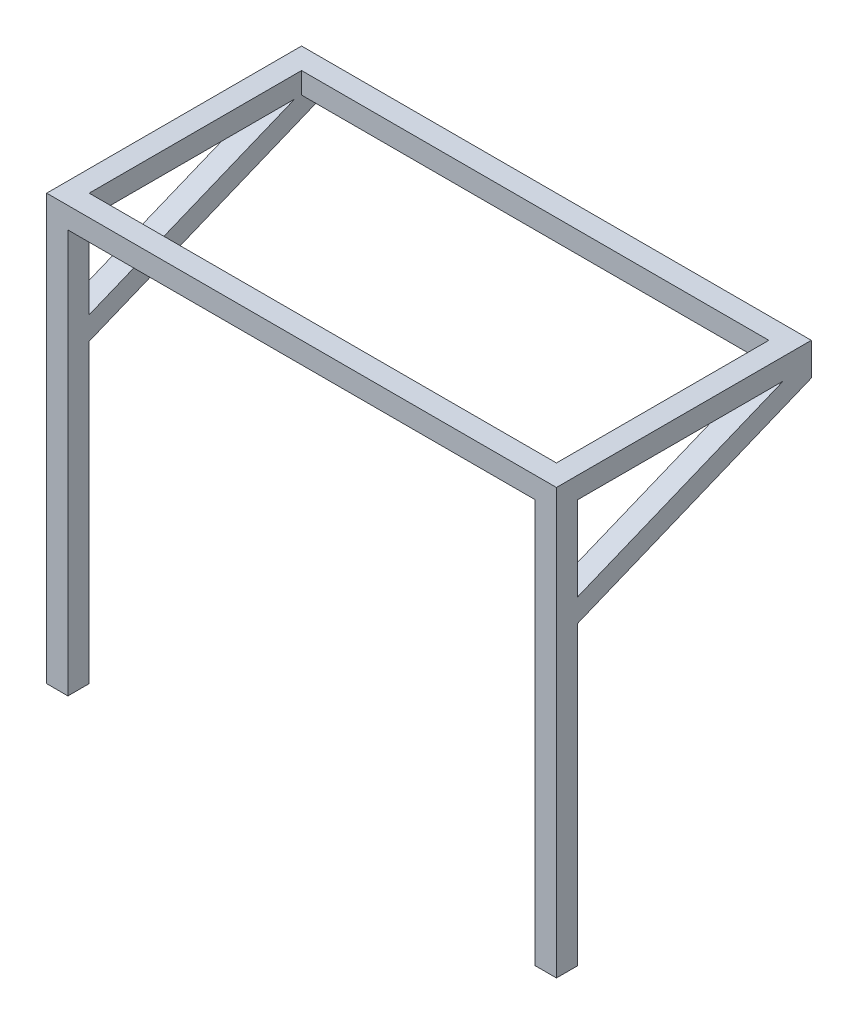
SolidWorks part; units mm, degrees
ref_plane "Front Plane" through (0, 0, 0) normal (0, 0, 1) x (1, 0, 0)
ref_plane "Top Plane" through (0, 0, 0) normal (0, 1, 0) x (1, 0, 0)
ref_plane "Right Plane" through (0, 0, 0) normal (1, 0, 0) x (0, 0, -1)
sketch "Sketch1" plane through (0, 0, 0) normal (0, 1, 0) x (1, 0, 0)
  line L1 (0, 0) -> (609.6, 0)
  line L2 (0, 0) -> (0, 304.8)
  line L3 (0, 304.8) -> (609.6, 304.8)
  line L4 (609.6, 0) -> (609.6, 304.8)
  line L5 (0, 0) -> (25.4, 0)
  line L6 (0, 0) -> (0, 25.4)
  line L7 (0, 25.4) -> (25.4, 25.4)
  line L8 (25.4, 0) -> (25.4, 25.4)
  line L10 (0, 304.8) -> (0, 279.4)
  line L14 (609.6, 304.8) -> (609.6, 279.4)
  line L17 (609.6, 0) -> (584.2, 0)
  line L18 (609.6, 0) -> (609.6, 25.4)
  line L19 (609.6, 25.4) -> (584.2, 25.4)
  line L20 (584.2, 0) -> (584.2, 25.4)
  point P8 (0, 0)
  point P11 (0, 0)
  dimension "D1" = 609.6
  dimension "D2" = 304.8
  dimension "D3" = 25.4
extrude "Boss-Extrude1" add sketch "Sketch1" along normal mid plane 508 contours L1 L8 L7 L2 | L20 L1 L4 L19 region at (12.7, 0, -12.7) region at (596.9, 0, -12.7)
sketch "Sketch2" plane through (0, 254, 0) normal (0, 1, 0) x (1, 0, 0)
  line L28 (609.6, 0) -> (609.6, 25.4) construction
  line L29 (0, 25.4) -> (609.6, 25.4)
  line L30 (0, 25.4) -> (0, 304.8)
  line L31 (0, 304.8) -> (609.6, 304.8)
  line L32 (609.6, 25.4) -> (609.6, 304.8)
  line L33 (25.4, 0) -> (584.2, 0)
  line L34 (25.4, 0) -> (25.4, 25.4)
  line L36 (25.4, 25.4) -> (584.2, 25.4)
  line L37 (584.2, 0) -> (584.2, 25.4)
  line L38 (25.4, 25.4) -> (584.2, 25.4)
  line L39 (25.4, 25.4) -> (25.4, 279.4)
  line L40 (25.4, 279.4) -> (584.2, 279.4)
  line L41 (584.2, 25.4) -> (584.2, 279.4)
  dimension "D1" = 25.4
  dimension "D2" = 279.4
extrude "Boss-Extrude2" add sketch "Sketch2" against normal blind 25.4 contours L41 L29 L32 L31 L30 L39 L40 | L34 L33 L37 L36 region at (6.7058, 254, -165.1)
sketch "Sketch3" plane through (609.6, 0, 0) normal (1, 0, 0) x (0, 0, -1)
  line L0 (25.4, 114.3) -> (304.8, 228.6) construction
  line L1 (25.4, 228.6) -> (25.4, -254) construction
  line L2 (25.4, 228.6) -> (304.8, 228.6) construction
  line L3 (25.4, 100.5784) -> (304.8, 214.8784)
  line L4 (25.4, 128.0216) -> (304.8, 242.3216)
  line L5 (30.2086, 102.5456) -> (309.6086, 216.8456) construction
  line L6 (304.8, 254) -> (304.8, 214.8784)
  line L7 (25.4, 100.5784) -> (25.4, 128.0216)
  line L8 (20.5914, 126.0544) -> (299.9914, 240.3544) construction
  line L9 (304.8, 228.6) -> (304.8, 254) construction
  line M3 (25.4, -254) -> (25.4, 228.6)
  line M4 (25.4, 228.6) -> (304.8, 228.6)
  dimension "D1" = 114.3
  dimension "D2" = 12.7
  dimension "D3" = 12.7
extrude "Boss-Extrude3" add sketch "Sketch3" against normal blind 25.4 contours L6 L4 L3 M4 M3 region at (609.6, 169.5402, -161.1235)
sketch "Sketch4" plane through (0, 0, 0) normal (-1, 0, 0) x (0, 0, 1)
  line L0 (-271.2583, 228.6) -> (-25.4, 128.0216)
  line L1 (-25.4, 128.0216) -> (-25.4, 100.5784)
  line L2 (-25.4, 100.5784) -> (-304.8, 214.8784)
  line L3 (-304.8, 214.8784) -> (-304.8, 228.6)
  line L4 (-304.8, 228.6) -> (-271.2583, 228.6)
extrude "Boss-Extrude4" add sketch "Sketch4" against normal blind 25.4
